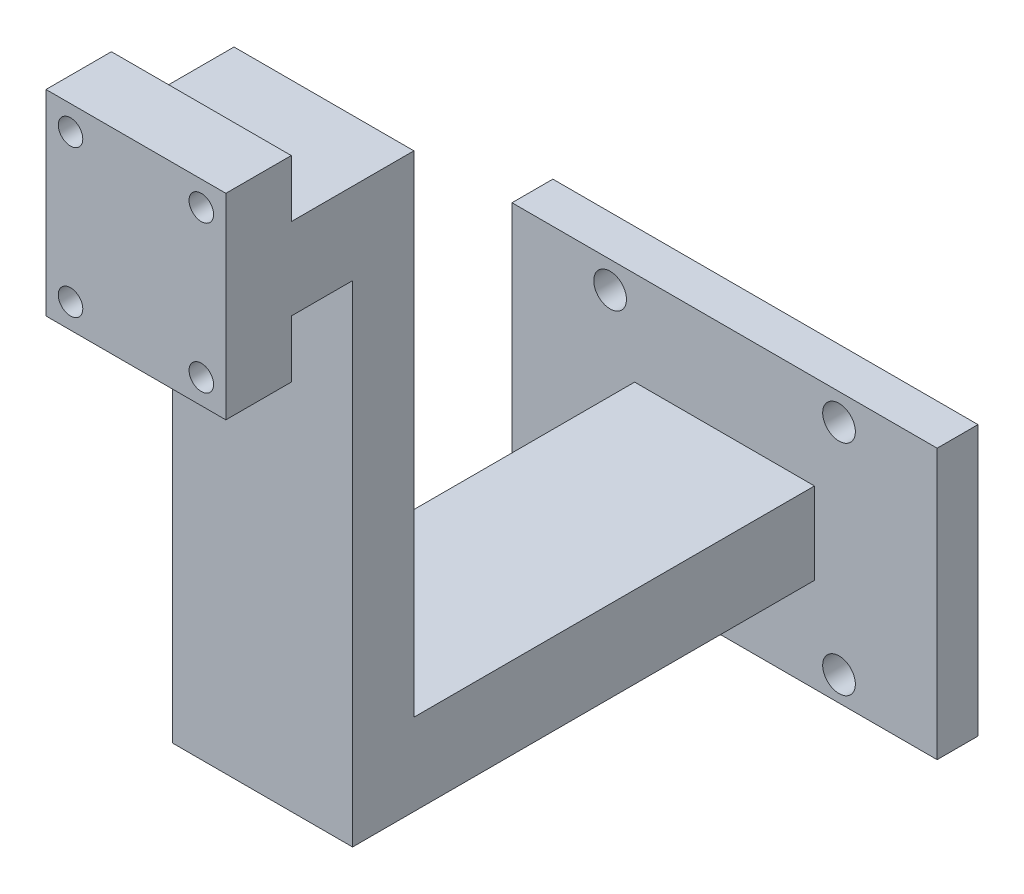
SolidWorks part; units mm, degrees
ref_plane "Front" through (0, 0, 0) normal (0, 0, 1) x (1, 0, 0)
ref_plane "Top" through (0, 0, 0) normal (0, 1, 0) x (1, 0, 0)
ref_plane "Right" through (0, 0, 0) normal (1, 0, 0) x (0, 0, -1)
sketch "Esquisse1" plane through (0, 0, 0) normal (0, 0, 1) x (1, 0, 0)
  line L1 (0, 0) -> (22, 0)
  line L2 (0, 0) -> (0, 24)
  line L3 (0, 24) -> (22, 24)
  line L4 (22, 0) -> (22, 24)
  line L5 (0, 17) -> (22, 17)
  line L6 (0, 17) -> (0, 7)
  line L7 (0, 7) -> (22, 7)
  line L8 (22, 17) -> (22, 7)
  circle A0 centre (3, 21) radius 1.5
  circle A1 centre (19, 21) radius 1.5
  circle A2 centre (19, 3) radius 1.5
  circle A3 centre (3, 3) radius 1.5
  dimension "D5" = 3
  dimension "D8" = 3
  dimension "D9" = 3
  dimension "D1" = 24
  dimension "D2" = 22
  dimension "D3" = 10
  dimension "D4" = 7
  dimension "D6" = 2
  dimension "D7" = 2
extrude "Boss.-Extru.1" add sketch "Esquisse1" along normal blind 8 contours L2 L5 L4 L3 A1 A0 | L2 L7 L4 L5 | L7 L2 L1 L4 A3 A2 region at (11, 3.5505, 0) region at (11, 12, 0) region at (11, 20.4495, 0)
extrude "Boss.-Extru.2" add sketch "Esquisse1<3>" against normal blind 15 contours L2 L7 L4 L5 region at (11, 12, 0)
sketch "Esquisse1<3>" plane through (0, 0, 0) normal (0, 0, 1) x (1, 0, 0) same geometry as "Esquisse1"
sketch "Esquisse2" plane through (0, 7, 0) normal (0, -1, 0) x (1, 0, 0)
  line L0 (22, -15) -> (22, 0) construction
  line L1 (0, -15) -> (22, -15)
  line L2 (0, -15) -> (0, -7.5)
  line L3 (0, -7.5) -> (22, -7.5)
  line L4 (22, -15) -> (22, -7.5)
  dimension "D1" = 7.5
extrude "Boss.-Extru.3" add sketch "Esquisse2" along normal blind 60
sketch "Esquisse3" plane through (0, 0, -15) normal (0, 0, -1) x (-1, 0, 0)
  line L0 (0, -53) -> (0, 17) construction
  line L1 (-22, -53) -> (0, -53)
  line L2 (-22, -53) -> (-22, -43)
  line L3 (-22, -43) -> (0, -43)
  line L4 (0, -53) -> (0, -43)
  dimension "D1" = 10
extrude "Boss.-Extru.4" add sketch "Esquisse3" along normal blind 54
sketch "Esquisse4" plane through (0, 0, -69) normal (0, 0, -1) x (-1, 0, 0)
  line L6 (-22, -43) -> (-22, 17) construction
  line L7 (-37, -31.5) -> (15, -31.5)
  line L8 (-37, -31.5) -> (-37, -64.5)
  line L9 (-37, -64.5) -> (15, -64.5)
  line L10 (15, -31.5) -> (15, -64.5)
  line L12 (-22, -53) -> (0, -53) construction
  dimension "D1" = 52
  dimension "D2" = 15
  dimension "D3" = 33
  dimension "D4" = 11.5
extrude "Boss.-Extru.5" add sketch "Esquisse4" against normal blind 5
sketch "Esquisse6" plane through (0, 0, -69) normal (0, 0, -1) x (-1, 0, 0)
  line L1 (-37, -31.5) -> (-37, -64.5) construction
  line L2 (15, -64.5) -> (15, -31.5) construction
  line L3 (-37, -64.5) -> (15, -64.5) construction
  circle A0 centre (-25, -34.75) radius 2
  circle A1 centre (-25, -61.5) radius 2
  circle A2 centre (3, -34.75) radius 2
  circle A3 centre (3, -61.5) radius 2
  point P6 (0, 0)
  dimension "D1" = 26.75
  dimension "D2" = 4
  dimension "D3" = 3
  dimension "D4" = 12
  dimension "D6" = 12
  dimension "D5" = 2
extrude "Enlèv. mat.-Extru.1" cut sketch "Esquisse6" against normal blind 5
